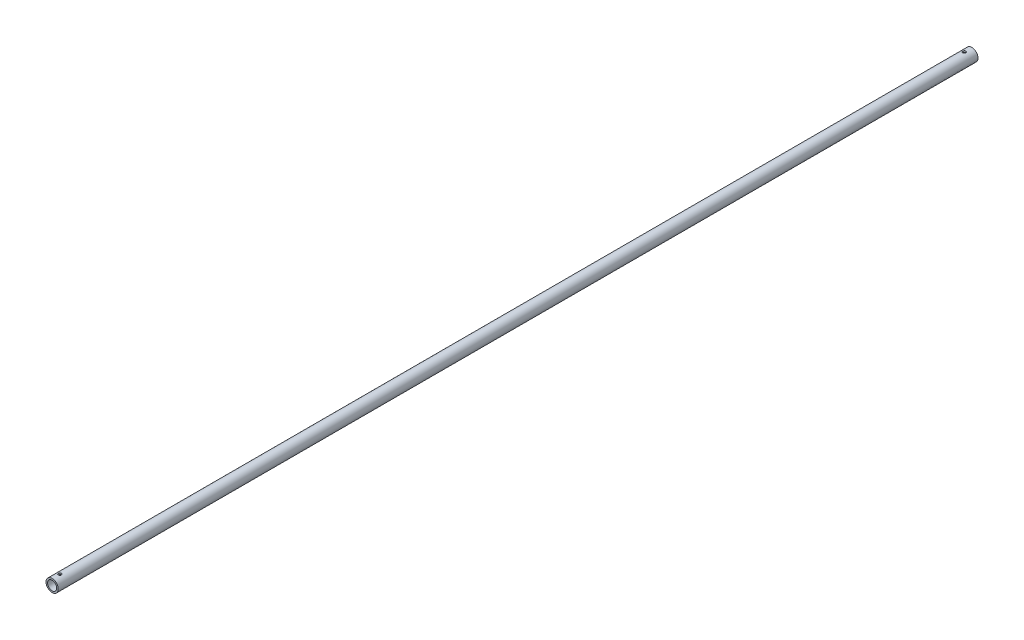
SolidWorks part; units mm, degrees
material "Thornel Mat VMA"
ref_plane "前视基准面" through (0, 0, 0) normal (0, 0, 1) x (1, 0, 0)
ref_plane "上视基准面" through (0, 0, 0) normal (0, 1, 0) x (1, 0, 0)
ref_plane "右视基准面" through (0, 0, 0) normal (1, 0, 0) x (0, 0, -1)
sketch "草图1" plane through (0, 0, 0) normal (0, 0, 1) x (1, 0, 0)
  circle A0 centre (0, 0) radius 3
  circle A1 centre (0, 0) radius 4
  dimension "D1" = 6
  dimension "D2" = 8
extrude "凸台-拉伸1" add sketch "草图1" along normal blind 300 and the other way blind 300
sketch "草图3" plane through (0, 0, 0) normal (0, 1, 0) x (1, 0, 0)
  line L0 (4, 300) -> (-4, 300) construction
  line L1 (-1000, 0) -> (49000, 0) construction
  circle A0 centre (0, 295) radius 1
  circle A1 centre (0, -295) radius 1
  dimension "D1" = 2
  dimension "D2" = 5
extrude "切除-拉伸2" cut sketch "草图3" against normal through all and the other way through all
sketch "草图5" plane through (0, 0, 0) normal (0, 1, 0) x (1, 0, 0)
  circle A0 centre (0, 0) radius 20.9079
